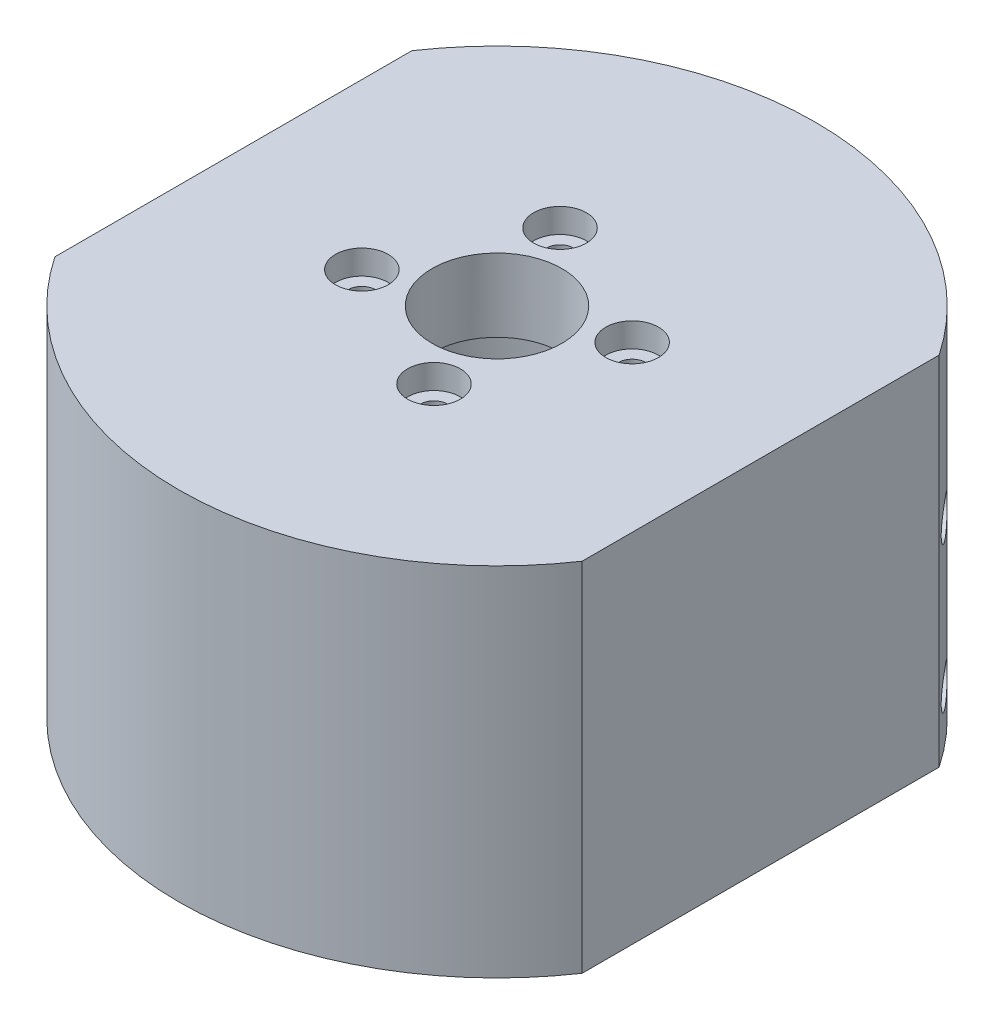
SolidWorks part; units mm, degrees
ref_plane "Front Plane" through (0, 0, 0) normal (0, 0, 1) x (1, 0, 0)
ref_plane "Top Plane" through (0, 0, 0) normal (0, 1, 0) x (1, 0, 0)
ref_plane "Right Plane" through (0, 0, 0) normal (1, 0, 0) x (0, 0, -1)
sketch "Sketch1" plane through (0, 0, 0) normal (0, 1, 0) x (1, 0, 0)
  line L0 (-32.5, 20.1696) -> (-32.5, -20.1696)
  line L1 (32.5, 20.1696) -> (32.5, -20.1696)
  line L2 (-32.5, 0) -> (32.5, 0) construction
  arc A0 (-32.5, -20.1696) -> (32.5, -20.1696) centre (0, 0) ccw
  arc A1 (32.5, 20.1696) -> (-32.5, 20.1696) centre (0, 0) ccw
  point P9 (0, 0)
  dimension "D1" = 65
  dimension "D2" = 76.5
extrude "Boss-Extrude1" add sketch "Sketch1" along normal blind 44
sketch "Sketch2" plane through (0, 44, 0) normal (0, 1, 0) x (1, 0, 0)
  line L0 (-4.4463, 12.216) -> (0, 0) construction
  line L1 (0, 13) -> (0, 0) construction
  circle A0 centre (0, 0) radius 13
  point P3 (-4.4463, 12.216)
  dimension "D1" = 26
  dimension "D2" = 20
hole_wizard "CBORE for M3 SHCS1" positions "Sketch2" profile "Sketch3" counterbore size "M3" standard "ANSI Metric" end condition through all
sketch "Sketch3" plane through (-4.4463, 44, -12.216) normal (1, 0, 0) x (0, 0, 1)
  line L0 (0, 0) -> (0, 44)
  line L1 (0, 44) -> (1.7, 44)
  line L3 (1.7, 44) -> (1.7, 3)
  line L4 (1.7, 3) -> (3.25, 3)
  line L5 (3.25, 3) -> (3.25, 0)
  line L7 (3.25, 0) -> (0, 0)
  line L11 (0, -6.35) -> (0, 107.95) construction
  dimension "Thru Hole Dia." = 3.4
  dimension "Thru Hole Depth" = 44
  dimension "C'Bore Dia." = 6.5
  dimension "C'Bore Depth" = 3
ref_axis "Axis1" through (0, 44, 0) along (0, -1, 0)
pattern_circular "CirPattern1" count 4 every 90 about axis through (0, 44, 0) along (0, -1, 0) of "CBORE for M3 SHCS1"
sketch "Sketch4" plane through (0, 0, 0) normal (0, -1, 0) x (1, 0, 0)
  circle A0 centre (0, 0) radius 16.2
  dimension "D1" = 32.4
extrude "Cut-Extrude1" cut sketch "Sketch4" against normal blind 35
sketch "Sketch5" plane through (0, 44, 0) normal (0, 1, 0) x (1, 0, 0)
  circle A0 centre (0, 0) radius 8
  dimension "D1" = 16
extrude "Cut-Extrude2" cut sketch "Sketch5" against normal through all
ref_plane "Plane1" through (0, 0, -38.25) normal (0, 0, -1) x (-1, 0, 0)
sketch "Sketch6" plane through (0, 0, -38.25) normal (0, 0, -1) x (-1, 0, 0)
  line L0 (-32.5, 44) -> (-32.5, 0) construction
  line L1 (-32.5, 0) -> (32.5, 0) construction
  circle A0 centre (-23.4, 6.85) radius 1.7
  dimension "D1" = 9.1
  dimension "D2" = 6.85
sketch "Sketch7" plane through (0, 0, 0) normal (0, -1, 0) x (1, 0, 0)
  line L0 (0, 38.25) -> (0, 39.25) construction
  line L1 (-32.5, 20.1696) -> (-32.5, 22.0071)
  line L2 (32.5, 20.1696) -> (32.5, 22.0071)
  line L3 (32.5, -20.1696) -> (32.5, -22.0071)
  line L4 (-32.5, -20.1696) -> (-32.5, -22.0071)
  arc A0 (-32.5, -20.1696) -> (32.5, -20.1696) centre (0, 0) ccw construction
  arc A1 (32.5, 20.1696) -> (-32.5, 20.1696) centre (0, 0) ccw construction
  arc A2 (-32.5, -20.1696) -> (32.5, -20.1696) centre (0, 0) ccw
  arc A3 (32.5, 20.1696) -> (-32.5, 20.1696) centre (0, 0) ccw
  circle A4 centre (0, 0) radius 39.25 construction
  arc A5 (-32.5, -22.0071) -> (32.5, -22.0071) centre (0, 0) ccw
  arc A6 (-32.5, 22.0071) -> (32.5, 22.0071) centre (0, 0) cw
  dimension "D1" = 1
extrude "Boss-Extrude2" add sketch "Sketch7" against normal up to surface (44 mm away) up to face at (0, 44, 8)
hole_wizard "CBORE for M4 SHCS1" positions "Sketch11" profile "Sketch12" counterbore size "M4" standard "ANSI Metric"
sketch "Sketch11" plane through (-50.0506, 69.222, -632.5589) normal (-1, 0, 0) x (0, -0.938, 0.3467)
  line L0 (253.0708, 554.1913) -> (269.9543, 547.9503) construction
  line L2 (261.5125, 551.0708) -> (258.0453, 541.6911) construction
  circle A0 centre (253.0708, 554.1913) radius 2.25
  circle A1 centre (269.9543, 547.9503) radius 2.25
  point P0 (253.0708, 554.1913)
  point P2 (269.9543, 547.9503)
sketch "Sketch12" plane through (-50.0506, 24, -25) normal (0, 1, 0) x (0, 0, 1)
  line L0 (0, 0) -> (0, 101.393)
  line L1 (0, 101.393) -> (2.15, 100.1012)
  line L2 (2.15, 100.1012) -> (2.15, 4)
  line L3 (2.15, 4) -> (4, 4)
  line L4 (4, 4) -> (4, 0)
  line L5 (4, 0) -> (0, 0)
  line L6 (0, 101.393) -> (-2.15, 100.1012) construction
  line L7 (0, -6.35) -> (0, 107.95) construction
  dimension "Hole Dia." = 4.3
  dimension "Hole Depth" = 100.1012
  dimension "C'Bore Dia." = 8
  dimension "C'Bore Depth" = 4
  dimension "Drill Angle" = 118
